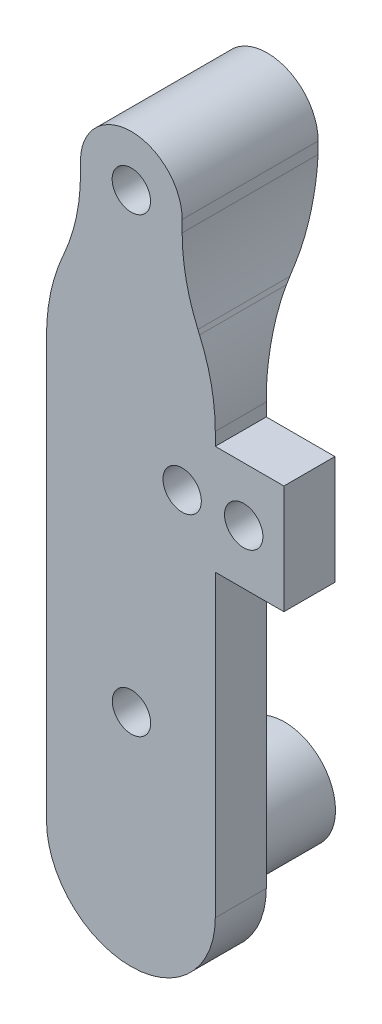
SolidWorks part; units mm, degrees
ref_plane "Front Plane" through (0, 0, 0) normal (0, 0, 1) x (1, 0, 0)
ref_plane "Top Plane" through (0, 0, 0) normal (0, 1, 0) x (1, 0, 0)
ref_plane "Right Plane" through (0, 0, 0) normal (1, 0, 0) x (0, 0, -1)
sketch "Sketch1" plane through (0, 0, 0) normal (0, 0, 1) x (1, 0, 0)
  line L0 (-5.898, 28.3342) -> (-5.898, 27.2476)
  line L1 (-2.8056, 11.5313) -> (-2.8056, 12.738)
  line L2 (3.6016, 11.5313) -> (3.6016, 1.3594)
  line L3 (-18.5662, 11.5313) -> (-18.5662, -26.5933)
  line L4 (3.6016, 1.3594) -> (-2.8056, 1.3594)
  line L5 (-2.8056, -26.5933) -> (-2.8056, 1.3594)
  line L6 (3.6016, 11.5313) -> (-2.8056, 11.5313)
  line L7 (-16.8793, 20.1661) -> (-17.0781, 19.7113)
  line L8 (-2.8056, 11.5313) -> (-18.5662, 11.5313) construction
  line L9 (-18.5662, 11.5313) -> (-18.5662, 12.5907)
  line L10 (-15.3912, 28.3342) -> (-15.3912, 27.2867)
  line L11 (-10.6859, -34.4736) -> (-36.5829, -34.4736) construction
  line L12 (-4.2728, 19.8107) -> (-4.4307, 20.1749)
  circle A0 centre (-10.6446, 28.3342) radius 1.7907
  circle A1 centre (-0.1512, 6.4513) radius 1.7907
  circle A2 centre (-5.898, 6.4513) radius 1.7907
  circle A3 centre (-10.6446, 28.3342) radius 4.7466
  circle A4 centre (-10.6859, -26.5933) radius 7.8803
  arc A5 (-18.5662, 12.5907) -> (-17.0781, 19.7113) centre (-0.7862, 12.5907) cw
  arc A6 (-15.3912, 27.2867) -> (-16.8793, 20.1661) centre (-33.1712, 27.2867) cw
  arc A7 (-5.898, 27.2476) -> (-4.4307, 20.1749) centre (11.882, 27.2476) ccw
  arc A8 (-2.8056, 12.738) -> (-4.2728, 19.8107) centre (-20.5856, 12.738) ccw
  circle A9 centre (-10.6287, -13.8687) radius 1.7907
  dimension "D1" = 17.78
  dimension "D2" = 3.5814
  dimension "D3" = 15.7606
  dimension "D4" = 3.5814
  dimension "D5" = 3.5814
  dimension "D6" = 7.9375
  dimension "D7" = 20.32
  dimension "D8" = 5.08
extrude "Boss-Extrude1" add sketch "Sketch1" along normal blind 12.7 contours A4 | L6 L8 L3 A4 L5 L4 L2 A2 A1 A9 | L8 L1 A8 L12 A7 L0 A3 L10 A6 L7 A5 L9 | A3 A0 region at (-10.6446, 23.7219, 0) region at (-9.8877, 1.7898, 0) region at (-10.6859, -26.5933, 0)
ref_plane "Plane2" through (0, -34.4736, 0) normal (0, -1, 0) x (-1, 0, 0)
sketch "Sketch5" plane through (-18.5662, 0, 0) normal (-1, 0, 0) x (0, 0, 1)
  line L0 (17.4625, -34.4736) -> (25.4, -34.4736)
  line L1 (25.4, -34.4736) -> (25.4, 27.6449)
  line L2 (7.9375, -34.4736) -> (0, -34.4736)
  line L3 (0, -34.4736) -> (0, 27.6449)
  line L4 (7.9375, 11.2679) -> (7.9375, 12.9164)
  line L5 (0, 10.6645) -> (25.4, 10.6645)
  line L6 (7.9375, -34.4736) -> (7.9375, 11.2679)
  line L7 (17.4625, -34.4736) -> (17.4625, 11.2679)
  line L8 (17.4625, 11.2679) -> (17.4625, 12.9164)
  line L9 (4.4886, 19.8842) -> (3.4489, 20.6771)
  line L10 (20.9114, 19.8842) -> (21.9511, 20.6771)
  line L12 (0, -26.5933) -> (0, 12.5907) construction
  line L14 (-6.985, -34.4736) -> (6.985, -34.4736) construction
  arc A0 (17.4625, 12.9164) -> (20.9114, 19.8842) centre (26.2255, 12.9164) cw
  arc A1 (7.9375, 12.9164) -> (4.4886, 19.8842) centre (-0.8255, 12.9164) ccw
  arc A2 (25.4, 27.6449) -> (21.9511, 20.6771) centre (16.637, 27.6449) cw
  arc A3 (0, 27.6449) -> (3.4489, 20.6771) centre (8.763, 27.6449) ccw
  line M1 (0, 12.5907) -> (0, -26.5933)
  line M2 (0, -26.5933) -> (12.7, -26.5933)
  line M4 (12.7, 12.5907) -> (0, 12.5907)
  dimension "D1" = 8.763
  dimension "D4" = 1.6485
  dimension "D2" = 62.1185
  dimension "D3" = 45.7414
extrude "Cut-Extrude1" cut sketch "Sketch5" against normal through all contours L6 L3 M2 | L2 L6 L3 M2 | L4 A1 L6 M4 M1 | A3 L3 A1 L9 M4 region at (-18.5662, -7.9644, 3.9687) region at (-18.5662, 11.6276, 3.9687) region at (-18.5662, -30.5334, 3.9687) region at (-18.5662, 16.935, 3.1586)
sketch "Sketch7" plane through (0, 0, 7.9375) normal (0, 0, -1) x (-1, 0, 0)
  line L0 (18.5662, -26.5933) -> (18.5662, 12.5907) construction
  circle A0 centre (10.6287, -26.5687) radius 4.7625
  circle A1 centre (10.6287, -13.8687) radius 1.7907 construction
  dimension "D1" = 9.525
  dimension "D2" = 7.9375
  dimension "D3" = 12.7
extrude "Boss-Extrude3" add sketch "Sketch7" along normal blind 9.525
